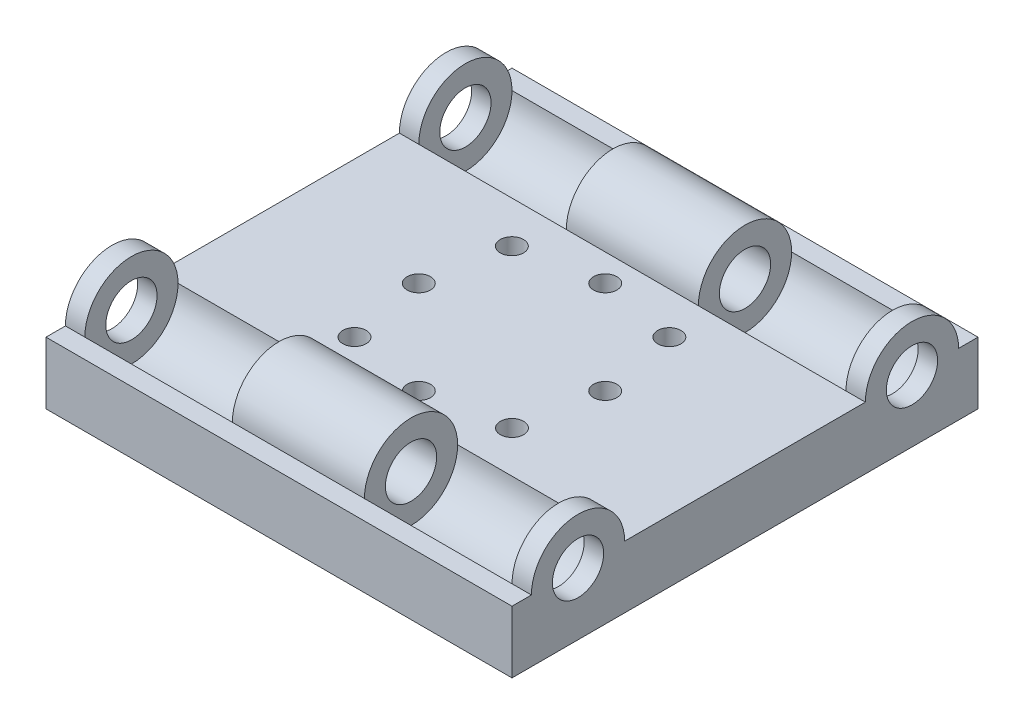
SolidWorks part; units mm, degrees
ref_plane "前视基准面" through (0, 0, 0) normal (0, 0, 1) x (1, 0, 0)
ref_plane "上视基准面" through (0, 0, 0) normal (0, 1, 0) x (1, 0, 0)
ref_plane "右视基准面" through (0, 0, 0) normal (1, 0, 0) x (0, 0, -1)
sketch "草图11" plane through (0, 0, 0) normal (1, 0, 0) x (0, 0, -1)
  line L0 (7.2289, 1.7435) -> (7.2289, -8.9847) construction
  line L2 (-22.7711, -3.2565) -> (-22.7711, -11.2565)
  line L3 (-22.7711, -11.2565) -> (37.2289, -11.2565)
  line L4 (37.2289, -3.2565) -> (37.2289, -11.2565)
  line L5 (-20.2711, -3.2565) -> (-22.7711, -3.2565)
  line L6 (-8.2711, -3.2565) -> (22.7289, -3.2565)
  line L7 (34.7289, -3.2565) -> (37.2289, -3.2565)
  arc A0 (-8.2711, -3.2565) -> (-20.2711, -3.2565) centre (-14.2711, -3.2565) ccw
  circle A1 centre (-14.2711, -3.2565) radius 3.3
  circle A2 centre (28.7289, -3.2565) radius 3.3
  arc A3 (22.7289, -3.2565) -> (34.7289, -3.2565) centre (28.7289, -3.2565) cw
  point P12 (-20.2711, -3.2565)
  point P13 (-8.2711, -3.2565)
  point P14 (22.7289, -3.2565)
  point P15 (34.7289, -3.2565)
  dimension "D3" = 12
  dimension "D4" = 6.6
  dimension "D1" = 60
  dimension "D2" = 43
  dimension "D5" = 8.5
extrude "凸台-拉伸4" add sketch "草图11" against normal blind 60 contours A0 A1 | L4 L2 L3 A0 A3 | A3 A2 region at (0, -6.367, -7.2289)
ref_plane "基准面1" through (-2.5, 0, 0) normal (1, 0, 0) x (0, 0, -1)
sketch "草图17" plane through (-2.5, 0, 0) normal (1, 0, 0) x (0, 0, -1)
  circle A2 centre (-14.2711, -3.2565) radius 6
extrude "切除-拉伸3" cut sketch "草图17" against normal blind 19
sketch "草图18" plane through (-2.5, 0, 0) normal (1, 0, 0) x (0, 0, -1)
  circle A0 centre (28.7289, -3.2565) radius 6
extrude "切除-拉伸4" cut sketch "草图18" against normal blind 19
ref_plane "基准面2" through (-57.5, 0, 0) normal (-1, 0, 0) x (0, 0, 1)
sketch "草图19" plane through (-57.5, 0, 0) normal (-1, 0, 0) x (0, 0, 1)
  circle A0 centre (-28.7289, -3.2565) radius 6
extrude "切除-拉伸5" cut sketch "草图19" against normal blind 19
sketch "草图21" plane through (-57.5, 0, 0) normal (-1, 0, 0) x (0, 0, 1)
  circle A0 centre (14.2711, -3.2565) radius 6
extrude "切除-拉伸6" cut sketch "草图21" against normal blind 19
sketch "草图22" plane through (0, -3.2565, 0) normal (0, 1, 0) x (1, 0, 0)
  line L0 (-38.5, 22.7289) -> (-21.5, 22.7289) construction
  line L1 (-2.5, -7.7) -> (-2.5, 7.7) construction
  line L2 (-60, -8.2711) -> (-60, 22.7289) construction
  line L11 (0, -8.2711) -> (0, 22.7289) construction
  line L12 (-90.1481, 7.2289) -> (31.1903, 7.2289) construction
  circle A1 centre (-30, 19.2289) radius 1.5
  circle A3 centre (-30, -4.7711) radius 1.5
  circle A4 centre (-18, 7.2289) radius 1.5
  circle A5 centre (-42, 7.2289) radius 1.5
  circle A6 centre (-19.87, 17.3589) radius 1.5
  circle A10 centre (-19.87, -2.9011) radius 1.5
  circle A11 centre (-40.15, -2.9011) radius 1.5
  circle A12 centre (-40.15, 17.3589) radius 1.5
  point P11 (-30, 7.2289)
  point P12 (-30, 7.2289)
  dimension "D2" = 3
  dimension "D3" = 3
  dimension "D6" = 12
  dimension "D9" = 15.5
  dimension "D10" = 3
  dimension "D11" = 3
  dimension "D12" = 3
  dimension "D13" = 20.28
  dimension "D14" = 10.13
  dimension "D15" = 20.28
  dimension "D19" = 10.13
  dimension "D1" = 12
  dimension "D4" = 15.5
  dimension "D5" = 30
  dimension "D7" = 12
  dimension "D8" = 12
  dimension "D16" = 10.13
  dimension "D17" = 19.87
  dimension "D18" = 19.87
  dimension "D20" = 10.13
extrude "切除-拉伸7" cut sketch "草图22" against normal blind 100
sketch "草图28" plane through (0, -11.2565, 0) normal (0, -1, 0) x (1, 0, 0)
  circle A0 centre (-19.87, 2.9011) radius 3
  circle A1 centre (-19.87, -17.3589) radius 3
  circle A2 centre (-40.15, -17.3589) radius 3
  circle A3 centre (-40.15, 2.9011) radius 3
  point P3 (-30, -7.2289)
extrude "凸台-拉伸5" add sketch "草图28" along normal blind 1.5
chamfer "倒角1" distance 1.5 distance2 0.5 4 edges at (-19.87, -12.7565, -20.3589) (-40.15, -12.7565, -20.3589) (-40.15, -12.7565, -0.0989) (-19.87, -12.7565, -0.0989) first distance on face at (-19.87, -12.7565, -20.3589) first distance on face at (-40.15, -12.7565, -20.3589) first distance on face at (-40.15, -12.7565, -0.0989) first distance on face at (-19.87, -12.7565, -0.0989)
sketch "草图29" plane through (0, -11.2565, 0) normal (0, 1, 0) x (1, 0, 0)
  circle A0 centre (-40.15, -2.9011) radius 1.5
  circle A1 centre (-40.15, 17.3589) radius 1.5
  circle A2 centre (-19.87, 17.3589) radius 1.5
  circle A3 centre (-19.87, -2.9011) radius 1.5
  point P3 (-30, 7.2289)
extrude "切除-拉伸9" cut sketch "草图29" against normal through all
